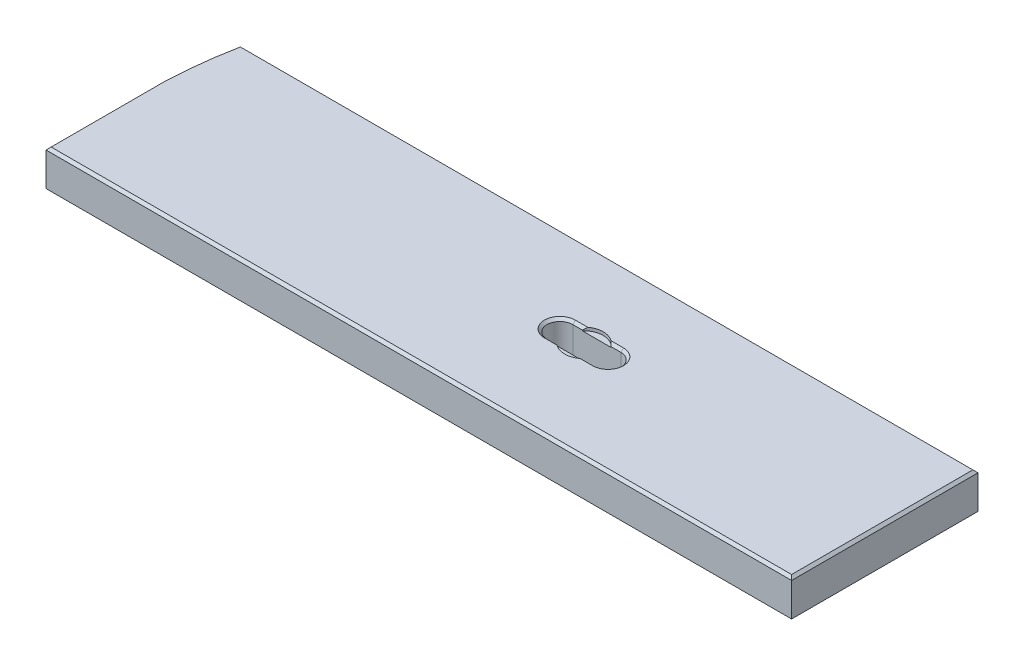
SolidWorks part; units mm, degrees
material "Oak"
ref_plane "Front Plane" through (0, 0, 0) normal (0, 0, 1) x (1, 0, 0)
ref_plane "Top Plane" through (0, 0, 0) normal (0, 1, 0) x (1, 0, 0)
ref_plane "Right Plane" through (0, 0, 0) normal (1, 0, 0) x (0, 0, -1)
sketch "Sketch1" plane through (0, 0, 0) normal (0, 1, 0) x (1, 0, 0)
  line L0 (433.343, 85.4392) -> (433.343, 194.4655) construction
  line L1 (0, 0) -> (736.6, 0)
  line L2 (0, 0) -> (0, 184.15)
  line L3 (0, 184.15) -> (736.6, 184.15)
  line L4 (736.6, 0) -> (736.6, 184.15)
  line L6 (409.5623, 110.8392) -> (457.1238, 110.8392)
  line L8 (409.5623, 85.4392) -> (457.1238, 85.4392)
  arc A4 (457.1238, 85.4392) -> (457.1238, 110.8392) centre (457.1238, 98.1392) ccw
  arc A5 (409.5623, 110.8392) -> (409.5623, 85.4392) centre (409.5623, 98.1392) ccw
  point P14 (457.1238, 110.8392)
  dimension "D7" = 25.4
  dimension "D1" = 184.15
  dimension "D2" = 736.6
  dimension "D3" = 47.5615
  dimension "D4" = 98.1393
  dimension "D5" = 457.1238
extrude "Boss-Extrude1" add sketch "Sketch1" along normal blind 38.1
sketch "Sketch4" plane through (0, 0, 0) normal (0, -1, 0) x (1, 0, 0)
  line L0 (0, -184.15) -> (0, 0) construction
  line L1 (0, -184.15) -> (0, -113.9573)
  line L2 (736.6, -184.15) -> (0, -184.15) construction
  line L3 (8.3432, -184.15) -> (0, -184.15)
  arc A1 (0, -113.9573) -> (8.3432, -184.15) centre (433.324, -98.044) ccw
  dimension "D1" = 433.324
  dimension "D3" = 433.6161
  dimension "D2" = 98.044
extrude "Cut-Extrude2" cut sketch "Sketch4" against normal through all
chamfer "Chamfer1" distance 2.54 angle 45 9 edges at (372.4716, 38.1, -184.15) (736.6, 38.1, -92.075) (368.3, 38.1, 0) (0, 38.1, -56.9787) (433.343, 38.1, -110.8392) (433.343, 38.1, -85.4392) (396.8623, 38.1, -98.1392) (469.8238, 38.1, -98.1392) (2.7389, 38.1, -149.2239)
chamfer "Chamfer2" distance 2.54 angle 45 9 edges at (433.343, 0, -110.8392) (433.343, 0, -85.4392) (368.3, 0, 0) (736.6, 0, -92.075) (372.4716, 0, -184.15) (0, 0, -56.9787) (396.8623, 0, -98.1392) (469.8238, 0, -98.1392) (2.7389, 0, -149.2239)
sketch "Sketch2" plane through (0, 38.1, 0) normal (0, 1, 0) x (1, 0, 0)
  line L0 (409.5623, 98.1392) -> (457.1238, 98.1392) construction
  circle A0 centre (433.343, 98.1392) radius 19.05
  dimension "D1" = 38.1
extrude "Cut-Extrude1" cut sketch "Sketch2" against normal blind 3.175
